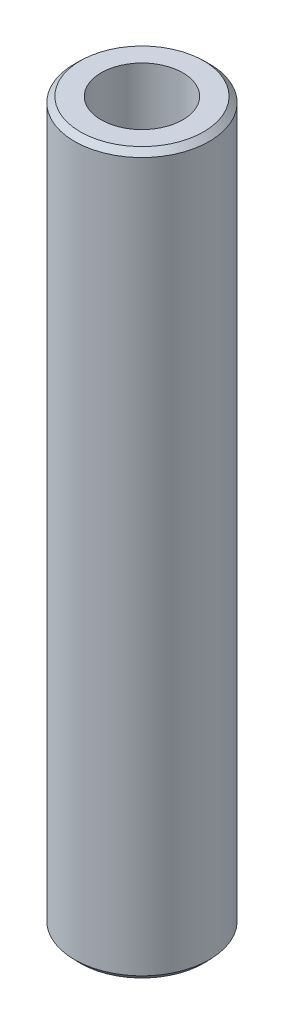
SolidWorks part; units mm, degrees
ref_plane "Front Plane" through (0, 0, 0) normal (0, 0, 1) x (1, 0, 0)
ref_plane "Top Plane" through (0, 0, 0) normal (0, 1, 0) x (1, 0, 0)
ref_plane "Right Plane" through (0, 0, 0) normal (1, 0, 0) x (0, 0, -1)
sketch "Sketch1" plane through (0, 0, 0) normal (0, 1, 0) x (1, 0, 0)
  circle A0 centre (0, 0) radius 55
  dimension "SHAFT_OD" = 110
extrude "Boss-Extrude1" add sketch "Sketch1" along normal blind 587.9105
sketch "Sketch2" plane through (0, 0, 0) normal (0, 1, 0) x (1, 0, 0)
  circle A0 centre (0, 0) radius 33.3338
  dimension "BORE_D" = 66.6676
extrude "Cut-Extrude1" cut sketch "Sketch2" along normal through all
chamfer "Chamfer1" distance 4.4517 angle 46.388 2 edges at (0, 587.9105, 55) (0, 0, 55) first distance on face at (0, 587.9105, 55) first distance on face at (0, 0, 33.3338)
